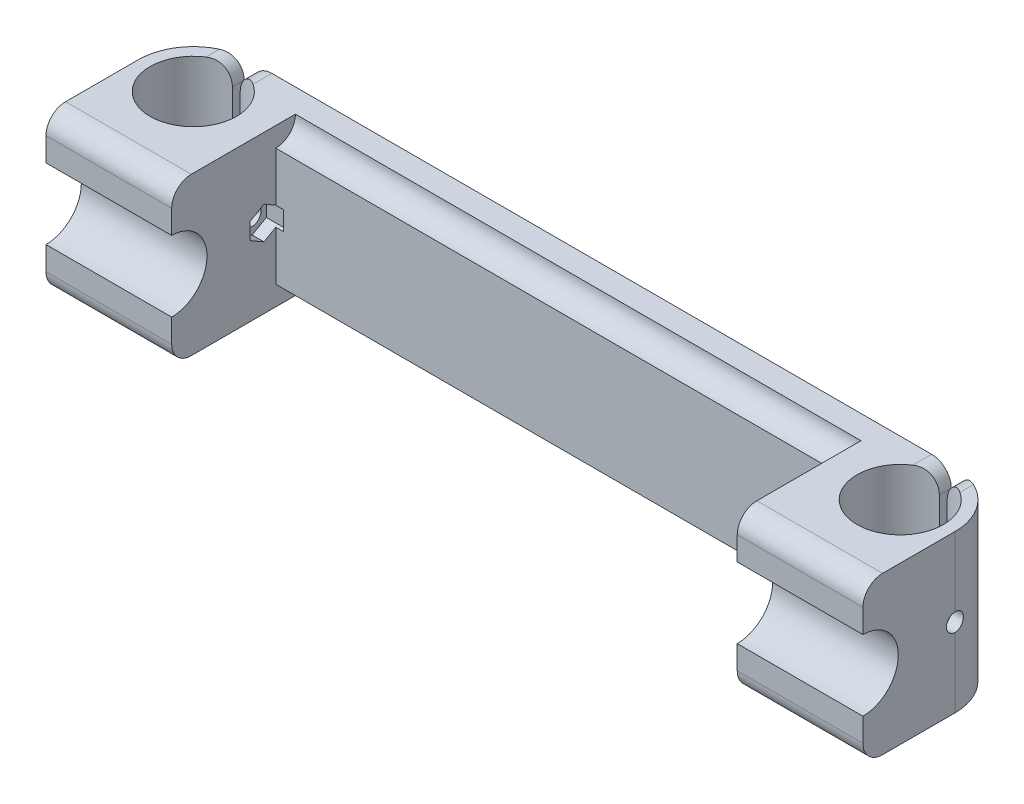
SolidWorks part; units mm, degrees
ref_plane "Front Plane" through (0, 0, 0) normal (0, 0, 1) x (1, 0, 0)
ref_plane "Top Plane" through (0, 0, 0) normal (0, 1, 0) x (1, 0, 0)
ref_plane "Right Plane" through (0, 0, 0) normal (1, 0, 0) x (0, 0, -1)
sketch "Sketch1" plane through (0, 0, 0) normal (0, 1, 0) x (1, 0, 0)
  line L0 (137.4606, -14.5) -> (119.4606, -14.5)
  line L1 (119.4606, -14.5) -> (119.4606, 7.5)
  line L2 (-42.5394, -14.5) -> (-24.5394, -14.5)
  line L3 (-42.5394, 13.5) -> (137.4606, 13.5)
  line L4 (119.4606, 7.5) -> (-24.5394, 7.5)
  line L5 (-24.5394, -14.5) -> (-24.5394, 7.5)
  line L6 (-56.5394, -0.5) -> (-56.5394, -14.5)
  line L7 (-56.5394, -14.5) -> (-42.5394, -14.5)
  line L8 (137.4606, -14.5) -> (151.4606, -14.5)
  line L9 (151.4606, -14.5) -> (151.4606, -0.5)
  circle A0 centre (-42.5394, -0.5) radius 11
  circle A1 centre (137.4606, -0.5) radius 11
  arc A2 (-56.5394, -0.5) -> (-42.5394, 13.5) centre (-42.5394, -0.5) cw
  arc A6 (137.4606, 13.5) -> (151.4606, -0.5) centre (137.4606, -0.5) cw
  dimension "D3" = 22
  dimension "D4" = 22
  dimension "D5" = 180
  dimension "D6" = 3
  dimension "D1" = 18
  dimension "D2" = 18
  dimension "D8" = 6
extrude "Boss-Extrude1" add sketch "Sketch1" along normal blind 40
sketch "Sketch2" plane through (-56.5394, 0, 0) normal (-1, 0, 0) x (0, 0, 1)
  line L0 (14.5, 40) -> (19, 40)
  line L1 (24, 35) -> (24, 29)
  line L2 (24, 11) -> (24, 5)
  line L3 (19, 0) -> (14.5, 0)
  line L4 (14.5, 0) -> (14.5, 40)
  arc A0 (24, 29) -> (24, 11) centre (24, 20) ccw
  arc A1 (24, 5) -> (19, 0) centre (19, 5) cw
  arc A2 (19, 40) -> (24, 35) centre (19, 35) cw
  point P11 (24, 0)
  dimension "D1" = 9
  dimension "D3" = 5
  dimension "D2" = 9.5
extrude "Boss-Extrude2" add sketch "Sketch2" against normal up to surface (32 mm away) up to face at (-24.5394, 20, 3.5)
ref_plane "Plane1" through (47.4606, 0, 0) normal (-1, 0, 0) x (0, 0, 1)
sketch "Sketch3" plane through (151.4606, 0, 0) normal (1, 0, 0) x (0, 0, -1)
  line L0 (-14.5, 0) -> (-14.5, 40)
  line L5 (-19, 0) -> (7.5, 0)
  line L6 (7.5, 0) -> (7.5, 40)
  line L7 (7.5, 40) -> (-19, 40)
  line L8 (-24, 35) -> (-24, 29)
  line L9 (-24, 11) -> (-24, 5)
  line L10 (-19, 0) -> (-14.5, 0)
  line L12 (-14.5, 40) -> (-19, 40)
  line L13 (-24, 35) -> (-24, 29)
  line L14 (-24, 11) -> (-24, 5)
  line L15 (7.5, 0) -> (7.5, 40)
  arc A3 (-19, 40) -> (-24, 35) centre (-19, 35) ccw
  arc A4 (-24, 11) -> (-24, 29) centre (-24, 20) ccw
  arc A5 (-24, 5) -> (-19, 0) centre (-19, 5) ccw
  arc A6 (-19, 40) -> (-24, 35) centre (-19, 35) ccw
  arc A7 (-24, 11) -> (-24, 29) centre (-24, 20) ccw
  arc A8 (-24, 5) -> (-19, 0) centre (-19, 5) ccw
  line M12 (-14.5, 40) -> (-14.5, 0)
  dimension "D1" = 0
sketch "Sketch4" plane through (0, 0, -7.5) normal (0, 0, 1) x (1, 0, 0)
  line L0 (119.4606, 40) -> (119.4606, 0) construction
  line L1 (119.4606, 35) -> (-24.5394, 35)
  line L2 (119.4606, 35) -> (119.4606, 5)
  line L3 (119.4606, 5) -> (-24.5394, 5)
  line L4 (-24.5394, 35) -> (-24.5394, 5)
  line L5 (-24.5394, 40) -> (-24.5394, 0) construction
  line L6 (-24.5394, 0) -> (119.4606, 0) construction
  dimension "D1" = 5
  dimension "D2" = 30
extrude "Boss-Extrude4" add sketch "Sketch4" along normal blind 5
fillet "Fillet1" radius 5 2 edges at (47.4606, 35, -7.5) (47.4606, 5, -7.5)
extrude "Boss-Extrude5" add sketch "Sketch3" against normal up to surface (32 mm away) contours L14 A8 L10 L12 A6 L13 A7 M12 region at (151.4606, 0.4111, 16.75) up to face at (119.4606, 20, 1.1548)
sketch "Sketch5" plane through (0, 0, -13.5) normal (0, 0, -1) x (-1, 0, 0)
  line L0 (-137.4606, 20) -> (42.5394, 20) construction
  line L1 (-137.4606, 40) -> (-137.4606, 0) construction
  line L2 (42.5394, 40) -> (42.5394, 0) construction
  line L3 (-137.4606, 40) -> (42.5394, 40) construction
  line L4 (32.5394, 35) -> (-127.4606, 35)
  line L5 (37.5394, 30) -> (37.5394, 10)
  line L6 (32.5394, 5) -> (-127.4606, 5)
  line L7 (-132.4606, 30) -> (-132.4606, 10)
  line L8 (37.5394, 35) -> (-132.4606, 5) construction
  line L9 (37.5394, 5) -> (-132.4606, 35) construction
  arc A0 (32.5394, 35) -> (37.5394, 30) centre (32.5394, 30) cw
  arc A1 (37.5394, 10) -> (32.5394, 5) centre (32.5394, 10) cw
  arc A2 (-127.4606, 5) -> (-132.4606, 10) centre (-127.4606, 10) cw
  arc A3 (-127.4606, 35) -> (-132.4606, 30) centre (-127.4606, 30) ccw
  point P6 (-47.4606, 20)
  dimension "D3" = 5
  dimension "D1" = 5
  dimension "D2" = 5
extrude "Cut-Extrude2" cut sketch "Sketch5" against normal blind 3
sketch "Sketch6" plane through (0, 0, -10.5) normal (0, 0, -1) x (-1, 0, 0)
  line L0 (-47.4606, 35) -> (-47.4606, 5) construction
  line L1 (32.5394, 35) -> (-127.4606, 35) construction
  line L2 (-127.4606, 5) -> (32.5394, 5) construction
  line L4 (12.5394, 10) -> (-107.4606, 10)
  line L5 (12.5394, 10) -> (12.5394, 30)
  line L6 (12.5394, 30) -> (-107.4606, 30)
  line L7 (-107.4606, 10) -> (-107.4606, 30)
  line L8 (12.5394, 10) -> (-107.4606, 30) construction
  line L9 (12.5394, 30) -> (-107.4606, 10) construction
  point P6 (-47.4606, 20)
  dimension "D1" = 120
  dimension "D2" = 20
extrude "Cut-Extrude3" cut sketch "Sketch6" against normal blind 5
sketch "Sketch8" plane through (0, 0, -13.5) normal (0, 0, -1) x (-1, 0, 0)
  line L0 (-137.4606, 40) -> (-137.4606, 0)
  line L1 (42.5394, 40) -> (42.5394, 0)
extrude "Cut-Extrude-Thin1" cut sketch "Sketch8" against normal blind 18 thin thin type mid plane wall 2
fillet "Fillet2" radius 5 8 edges at (-43.5394, 40, -11.9593) (-41.5394, 40, -11.9772) (-43.5394, 0, -11.9593) (-41.5394, 0, -11.9772) (136.4606, 0, -11.9772) (138.4606, 0, -11.9593) (138.4606, 40, -11.9593) (136.4606, 40, -11.9772)
sketch "Sketch9" plane through (151.4606, 0, 0) normal (1, 0, 0) x (0, 0, -1)
  line L0 (-0.5, 40) -> (-0.5, 0) construction
  circle A0 centre (-0.5, 20) radius 2.25
  dimension "D1" = 4.5
extrude "Cut-Extrude4" cut sketch "Sketch9" against normal blind 226
sketch "Sketch10" plane through (-24.5394, 0, 0) normal (1, 0, 0) x (0, 0, -1)
  line L1 (-0.5, 24.1569) -> (-4.1, 22.0785)
  line L2 (-4.1, 22.0785) -> (-4.1, 17.9215)
  line L3 (-4.1, 17.9215) -> (-0.5, 15.8431)
  line L4 (-0.5, 15.8431) -> (3.1, 17.9215)
  line L5 (3.1, 17.9215) -> (3.1, 22.0785)
  line L6 (3.1, 22.0785) -> (-0.5, 24.1569)
  circle A0 centre (-0.5, 20) radius 3.6 construction
  dimension "D1" = 7.2
extrude "Cut-Extrude5" cut sketch "Sketch10" against normal blind 3 and the other way blind 2
mirror "Mirror5" about plane through (47.4606, 0, 0) normal (-1, 0, 0) of "Cut-Extrude5"
